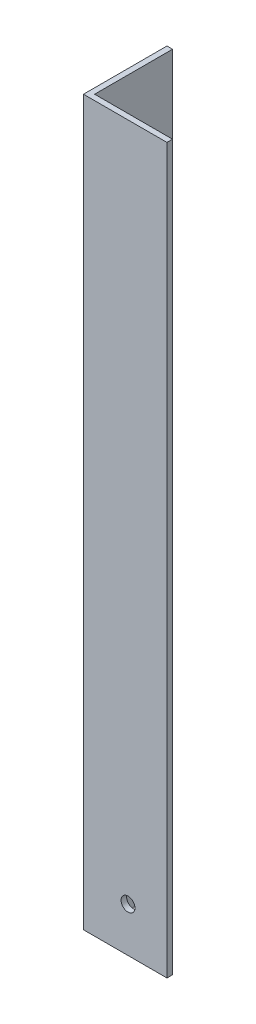
SolidWorks part; units mm, degrees
ref_plane "正面" through (0, 0, 0) normal (0, 0, 1) x (1, 0, 0)
ref_plane "平面" through (0, 0, 0) normal (0, 1, 0) x (1, 0, 0)
ref_plane "右側面" through (0, 0, 0) normal (1, 0, 0) x (0, 0, -1)
sketch "ｽｹｯﾁ1" plane through (0, 0, 0) normal (0, 1, 0) x (1, 0, 0)
  line L1 (0, 0) -> (15, 0)
  line L2 (0, 0) -> (0, -1)
  line L3 (0, -1) -> (15, -1)
  line L4 (15, 0) -> (15, -1)
  dimension "D1" = 15
  dimension "D2" = 1
sketch "ｽｹｯﾁ2" plane through (0, 0, 0) normal (0, 1, 0) x (1, 0, 0)
extrude "ﾎﾞｽ - 押し出し1" add sketch "ｽｹｯﾁ1" along normal blind 130
sketch "ｽｹｯﾁ3" plane through (0, 0, 0) normal (0, 0, -1) x (-1, 0, 0)
  line L1 (0, 130) -> (-1, 130)
  line L2 (0, 130) -> (0, 0)
  line L3 (0, 0) -> (-1, 0)
  line L4 (-1, 130) -> (-1, 0)
  dimension "D1" = 1
  dimension "D2" = 130
extrude "ﾎﾞｽ - 押し出し2" add sketch "ｽｹｯﾁ3" along normal blind 14
hole_wizard "M3x0.5 ねじ穴2" positions "ｽｹｯﾁ6" profile "ｽｹｯﾁ7" tap size "M3x0.5" standard "JIS" end condition through all
sketch "ｽｹｯﾁ6" plane through (0, 0, 1) normal (0, 0, 1) x (1, 0, 0)
  line L0 (8.25, 0) -> (-8.25, 0) construction
  line L1 (15, 130) -> (15, 0) construction
  point P0 (8, 8)
  dimension "D1" = 8
  dimension "D2" = 7
sketch "ｽｹｯﾁ7" plane through (8, 8, 1) normal (1, 0, 0) x (0, -1, 0)
  line L0 (0, 0) -> (0, 15)
  line L1 (0, 15) -> (1.25, 15)
  line L2 (1.25, 15) -> (1.25, 0)
  line L5 (1.25, 0) -> (0, 0)
  line L11 (0, -6.35) -> (0, 107.95) construction
  dimension "次ｻｰﾌｪｽまでのねじ下穴ﾄﾞﾘﾙ直径" = 2.5
  dimension "次ｻｰﾌｪｽまでのねじ下穴ﾄﾞﾘﾙの深さ" = 15
cosmetic thread "穴のねじ山2" parameters "D2"=3
